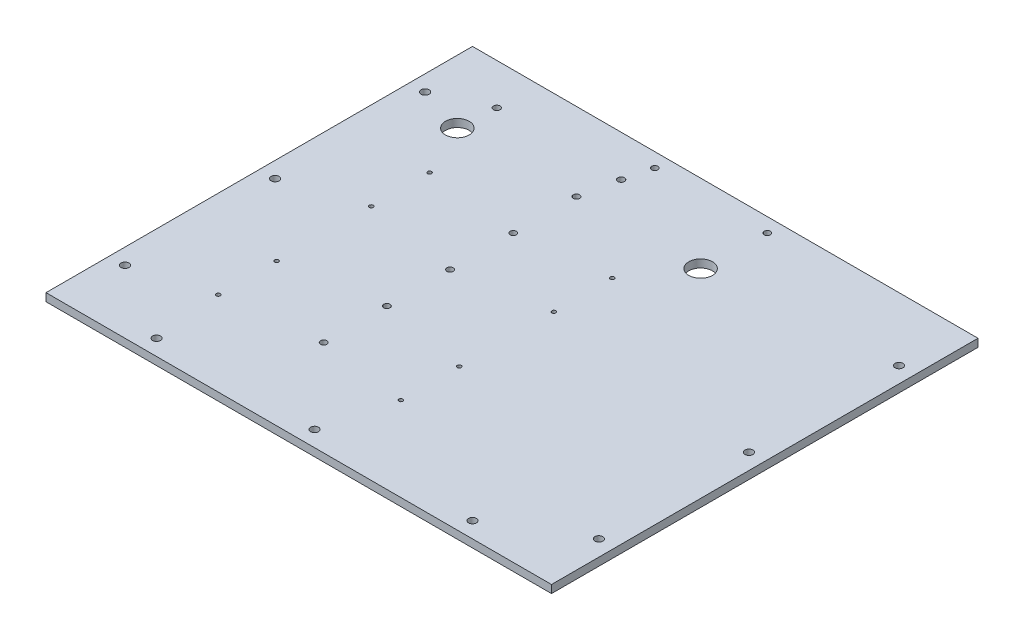
SolidWorks part; units mm, degrees
ref_plane "Front Plane" through (0, 0, 0) normal (0, 0, 1) x (1, 0, 0)
ref_plane "Top Plane" through (0, 0, 0) normal (0, 1, 0) x (1, 0, 0)
ref_plane "Right Plane" through (0, 0, 0) normal (1, 0, 0) x (0, 0, -1)
sketch "Sketch1" plane through (0, 0, 0) normal (0, 1, 0) x (1, 0, 0)
  line L0 (406.4, 0) -> (406.4, 342.9) construction
  line L1 (0, 0) -> (406.4, 0)
  line L2 (0, 0) -> (0, 342.9)
  line L3 (0, 342.9) -> (406.4, 342.9)
  line L4 (406.4, 0) -> (406.4, 342.9)
  line L5 (406.4, 0) -> (406.4, 342.9) construction
  line L6 (387.3669, 342.9) -> (384.1496, 342.9) construction
  line L7 (387.3669, 342.9) -> (384.1496, 342.9) construction
  point P9 (0, 0)
extrude "Boss-Extrude1" add sketch "Sketch1" along normal blind 6.35
sketch "Sketch3" plane through (0, 6.35, 0) normal (0, 1, 0) x (1, 0, 0)
  line L0 (0, 342.9) -> (0, 0) construction
  line L1 (25.4, 25.4) -> (381, 25.4) construction
  line L2 (25.4, 25.4) -> (25.4, 317.5) construction
  line L3 (25.4, 317.5) -> (381, 317.5) construction
  line L4 (381, 25.4) -> (381, 317.5) construction
  line L5 (0, 0) -> (406.4, 0) construction
  line L6 (406.4, 0) -> (406.4, 342.9) construction
  line L7 (406.4, 342.9) -> (0, 342.9) construction
  line L8 (0, 171.45) -> (406.4, 171.45) construction
  line L9 (203.2, 0) -> (203.2, 342.9) construction
  line L10 (12.7, 342.9) -> (12.7, 0) construction
  line L11 (393.7, 342.9) -> (393.7, 0) construction
  line L12 (406.4, 12.7) -> (0, 12.7) construction
  line L13 (12.7, 292.1) -> (393.7, 292.1) construction
  line L14 (12.7, 50.8) -> (393.7, 50.8) construction
  circle A0 centre (203.2, 12.7) radius 3.175
  circle A1 centre (330.2, 12.7) radius 3.175
  circle A2 centre (76.2, 12.7) radius 3.175
  circle A3 centre (12.7, 171.45) radius 3.175
  circle A4 centre (393.7, 171.45) radius 3.175
  circle A5 centre (12.7, 292.1) radius 3.175
  circle A6 centre (12.7, 50.8) radius 3.175
  circle A7 centre (393.7, 50.8) radius 3.175
  circle A8 centre (393.7, 292.1) radius 3.175
  dimension "D8" = 6.35
  dimension "D1" = 25.4
  dimension "D2" = 25.4
  dimension "D3" = 25.4
  dimension "D4" = 25.4
  dimension "D5" = 12.7
  dimension "D6" = 12.7
  dimension "D7" = 12.7
  dimension "D9" = 76.2
  dimension "D10" = 76.2
  dimension "D11" = 50.8
  dimension "D12" = 50.8
extrude "Cut-Extrude1" cut sketch "Sketch3" against normal through all
sketch "Sketch4" plane through (0, 6.35, 0) normal (0, 1, 0) x (1, 0, 0)
  line L0 (406.4, 342.9) -> (0, 342.9) construction
  line L1 (406.4, 0) -> (406.4, 342.9) construction
  line L2 (203.2, 342.9) -> (203.2, 0) construction
  line L3 (0, 0) -> (406.4, 0) construction
  line L4 (246.4, 279.9) -> (50.8, 279.9) construction
  line L5 (0, 342.9) -> (0, 0) construction
  line L6 (0, 342.9) -> (0, 0) construction
  line L7 (157.3728, 309.88) -> (147.7068, 309.88) construction
  line L8 (47.7068, 309.88) -> (57.3728, 309.88) construction
  line L9 (147.7068, 312.547) -> (157.3728, 312.547) construction
  line L10 (47.7068, 312.547) -> (57.3728, 312.547) construction
  line L11 (146.3548, 284.861) -> (146.3548, 275.336) construction
  line L12 (146.3548, 275.336) -> (146.3548, 234.061) construction
  line L13 (146.3548, 234.061) -> (146.3548, 224.536) construction
  line L14 (146.3548, 224.536) -> (146.3548, 183.261) construction
  line L15 (146.3548, 183.261) -> (146.3548, 173.736) construction
  line L16 (146.3548, 173.736) -> (146.3548, 132.461) construction
  line L17 (146.3548, 132.461) -> (146.3548, 122.936) construction
  line L18 (146.3548, 122.936) -> (146.3548, 81.661) construction
  line L19 (146.3548, 81.661) -> (146.3548, 72.136) construction
  circle A0 centre (246.4, 279.9) radius 9.525
  circle A1 centre (50.8, 279.9) radius 9.525
  circle A2 centre (217.5002, 67.7926) radius 1.5875 construction
  circle A3 centre (217.5002, 114.7318) radius 1.5875 construction
  circle A4 centre (70.6628, 114.7318) radius 1.5875 construction
  circle A5 centre (70.6628, 67.7926) radius 1.5875 construction
  circle A6 centre (70.6628, 190.8226) radius 1.5875 construction
  circle A7 centre (70.6628, 237.7618) radius 1.5875 construction
  circle A8 centre (217.5002, 237.7618) radius 1.5875 construction
  circle A9 centre (217.5002, 190.8226) radius 1.5875 construction
  circle A10 centre (217.5002, 67.7926) radius 1.5875
  circle A11 centre (217.5002, 114.7318) radius 1.5875
  circle A12 centre (70.6628, 114.7318) radius 1.5875
  circle A13 centre (70.6628, 67.7926) radius 1.5875
  circle A14 centre (70.6628, 190.8226) radius 1.5875
  circle A15 centre (70.6628, 237.7618) radius 1.5875
  circle A16 centre (217.5002, 237.7618) radius 1.5875
  circle A17 centre (217.5002, 190.8226) radius 1.5875
  circle A22 centre (248.4501, 331.47) radius 2.5 construction
  circle A23 centre (157.9499, 331.47) radius 2.5 construction
  circle A28 centre (248.4501, 331.47) radius 2.5
  circle A29 centre (157.9499, 331.47) radius 2.5
  arc A30 (47.7068, 312.547) -> (47.7068, 307.213) centre (47.7068, 309.88) ccw construction
  arc A31 (57.3728, 307.213) -> (57.3728, 312.547) centre (57.3728, 309.88) ccw construction
  arc A32 (147.7068, 312.547) -> (147.7068, 307.213) centre (147.7068, 309.88) ccw construction
  arc A33 (157.3728, 307.213) -> (157.3728, 312.547) centre (157.3728, 309.88) ccw construction
  arc A34 (47.7068, 312.547) -> (47.7068, 307.213) centre (47.7068, 309.88) ccw construction
  arc A35 (57.3728, 307.213) -> (57.3728, 312.547) centre (57.3728, 309.88) ccw construction
  arc A36 (147.7068, 312.547) -> (147.7068, 307.213) centre (147.7068, 309.88) ccw construction
  arc A37 (157.3728, 307.213) -> (157.3728, 312.547) centre (157.3728, 309.88) ccw construction
  circle A38 centre (52.5398, 309.88) radius 2.667
  circle A39 centre (152.5398, 309.88) radius 2.667
  arc A40 (148.8948, 81.661) -> (143.8148, 81.661) centre (146.3548, 81.661) ccw construction
  arc A41 (143.8148, 72.136) -> (148.8948, 72.136) centre (146.3548, 72.136) ccw construction
  arc A42 (143.8148, 122.936) -> (148.8948, 122.936) centre (146.3548, 122.936) ccw construction
  arc A43 (148.8948, 132.461) -> (143.8148, 132.461) centre (146.3548, 132.461) ccw construction
  arc A44 (143.8148, 173.736) -> (148.8948, 173.736) centre (146.3548, 173.736) ccw construction
  arc A45 (148.8948, 183.261) -> (143.8148, 183.261) centre (146.3548, 183.261) ccw construction
  arc A46 (143.8148, 224.536) -> (148.8948, 224.536) centre (146.3548, 224.536) ccw construction
  arc A47 (148.8948, 234.061) -> (143.8148, 234.061) centre (146.3548, 234.061) ccw construction
  arc A48 (143.8148, 275.336) -> (148.8948, 275.336) centre (146.3548, 275.336) ccw construction
  arc A49 (148.8948, 284.861) -> (143.8148, 284.861) centre (146.3548, 284.861) ccw construction
  arc A50 (148.8948, 81.661) -> (143.8148, 81.661) centre (146.3548, 81.661) ccw construction
  arc A51 (143.8148, 72.136) -> (148.8948, 72.136) centre (146.3548, 72.136) ccw construction
  arc A52 (143.8148, 122.936) -> (148.8948, 122.936) centre (146.3548, 122.936) ccw construction
  arc A53 (148.8948, 132.461) -> (143.8148, 132.461) centre (146.3548, 132.461) ccw construction
  arc A54 (143.8148, 173.736) -> (148.8948, 173.736) centre (146.3548, 173.736) ccw construction
  arc A55 (148.8948, 183.261) -> (143.8148, 183.261) centre (146.3548, 183.261) ccw construction
  arc A56 (143.8148, 224.536) -> (148.8948, 224.536) centre (146.3548, 224.536) ccw construction
  arc A57 (148.8948, 234.061) -> (143.8148, 234.061) centre (146.3548, 234.061) ccw construction
  arc A58 (143.8148, 275.336) -> (148.8948, 275.336) centre (146.3548, 275.336) ccw construction
  arc A59 (148.8948, 284.861) -> (143.8148, 284.861) centre (146.3548, 284.861) ccw construction
  circle A60 centre (146.3548, 178.4985) radius 2.54
  circle A61 centre (146.3548, 127.6985) radius 2.54
  circle A62 centre (146.3548, 76.8985) radius 2.54
  circle A63 centre (146.3548, 280.0985) radius 2.54
  circle A64 centre (146.3548, 229.2985) radius 2.54
  point P39 (0, 0)
  dimension "D1" = 19.05
  dimension "D2" = 63
  dimension "D3" = 160
  dimension "D4" = 342.9
  dimension "D5" = 50.8
extrude "Cut-Extrude2" cut sketch "Sketch4" against normal through all
equation "\"D9@Sketch3\"=3in"
